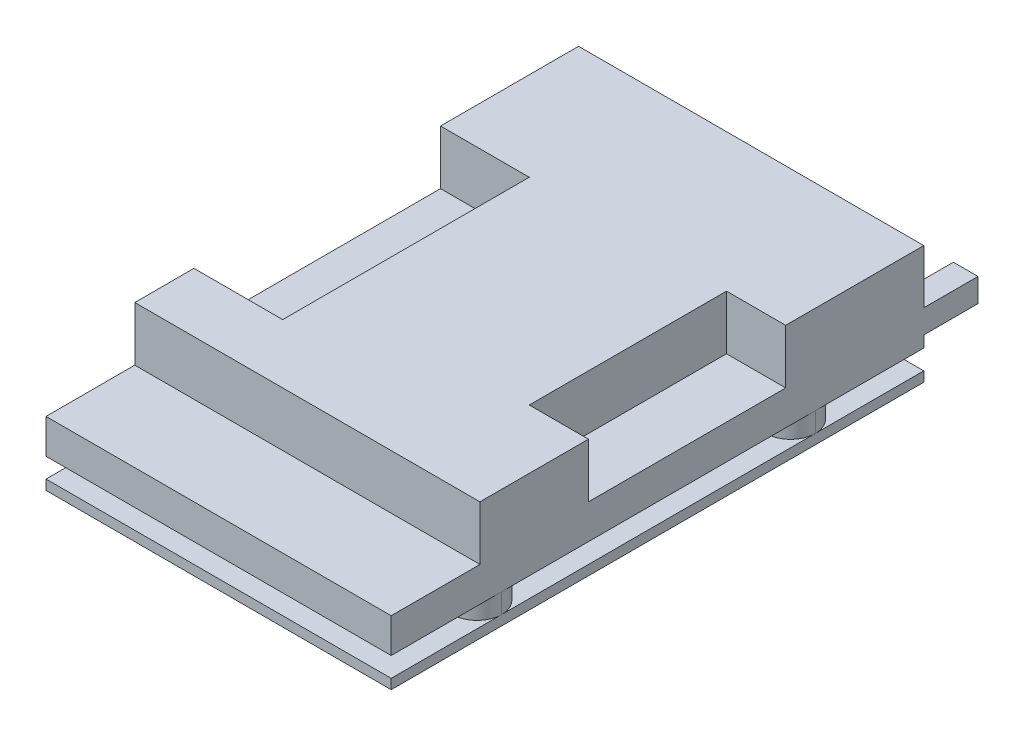
SolidWorks part; units mm, degrees
ref_plane "Front Plane" through (0, 0, 0) normal (0, 0, 1) x (1, 0, 0)
ref_plane "Top Plane" through (0, 0, 0) normal (0, 1, 0) x (1, 0, 0)
ref_plane "Right Plane" through (0, 0, 0) normal (1, 0, 0) x (0, 0, -1)
sketch "Sketch1" plane through (0, 0, 0) normal (0, 1, 0) x (1, 0, 0)
  line L1 (17.5, 27) -> (-17.5, 27)
  line L2 (17.5, 27) -> (17.5, -27)
  line L3 (17.5, -27) -> (-17.5, -27)
  line L4 (-17.5, 27) -> (-17.5, -27)
  line L5 (17.5, 27) -> (-17.5, -27) construction
  line L6 (17.5, -27) -> (-17.5, 27) construction
  point P0 (0, 0)
  dimension "D1" = 54
  dimension "D2" = 35
extrude "Boss-Extrude1" add sketch "Sketch1" along normal blind 12 contours L4 L3 L2 L1
sketch "Sketch2" plane through (0, 12, 0) normal (0, 1, 0) x (1, 0, 0)
  line L0 (17.5, 27) -> (17.5, -27) construction
  line L1 (-17.5, -27) -> (17.5, -27)
  line L2 (-17.5, -27) -> (-17.5, -18)
  line L3 (-17.5, -18) -> (17.5, -18)
  line L4 (17.5, -27) -> (17.5, -18)
  line L5 (-17.5, 27) -> (-17.5, -27) construction
  line L6 (-17.5, -12) -> (-8.5, -12)
  line L7 (-17.5, -12) -> (-17.5, 13)
  line L8 (-17.5, 13) -> (-8.5, 13)
  line L9 (-8.5, -12) -> (-8.5, 13)
  line L11 (17.5, 13) -> (11.5, 13)
  line L12 (17.5, 13) -> (17.5, -7)
  line L13 (17.5, -7) -> (11.5, -7)
  line L14 (11.5, 13) -> (11.5, -7)
  point P17 (17.5, 13.6612)
  dimension "D1" = 9
  dimension "D2" = 9
  dimension "D3" = 6
  dimension "D4" = 25
  dimension "D5" = 20
  dimension "D6" = 6
  dimension "D7" = 11
extrude "Cut-Extrude1" cut sketch "Sketch2" against normal blind 5.5
sketch "Sketch3" plane through (0, 0, -27) normal (0, 0, -1) x (-1, 0, 0)
  line L0 (-17.5, 0) -> (17.5, 0) construction
  line L1 (-12.5, 1) -> (12.5, 1)
  line L2 (-12.5, 1) -> (-12.5, 3)
  line L3 (-12.5, 3) -> (12.5, 3)
  line L4 (12.5, 1) -> (12.5, 3)
  line L5 (-17.5, 12) -> (-17.5, 0) construction
  line L6 (17.5, 12) -> (17.5, 0) construction
  dimension "D1" = 2
  dimension "D2" = 1
  dimension "D3" = 5
  dimension "D4" = 5
extrude "Cut-Extrude2" cut sketch "Sketch3" against normal through all both and the other way through all
sketch "Sketch4" plane through (-17.5, 0, 0) normal (-1, 0, 0) x (0, 0, 1)
  line L0 (27, 1) -> (-27, 1) construction
  line L1 (27, 1) -> (-27, 1)
  line L3 (-27, 1) -> (-18.5, 1)
  line L4 (-27, 1) -> (-27, 3)
  line L5 (-27, 3) -> (-18.5, 3)
  line L6 (-18.5, 1) -> (-18.5, 3)
  line L7 (-13.5, 1) -> (13.3, 1)
  line L8 (-13.5, 1) -> (-13.5, 3)
  line L9 (-13.5, 3) -> (13.3, 3)
  line L10 (13.3, 1) -> (13.3, 3)
  line L11 (27, 1) -> (18.3, 1)
  line L12 (27, 1) -> (27, 3)
  line L13 (27, 3) -> (18.3, 3)
  line L14 (18.3, 1) -> (18.3, 3)
  point P12 (0, 0)
  point P13 (0, 0)
  line M19 (-27, 12) -> (-27, 0)
  line M21 (27, 0) -> (27, 6.5)
  dimension "D1" = 5
  dimension "D2" = 5
  dimension "D3" = 2
  dimension "D4" = 8.5
  dimension "D5" = 8.7
extrude "Cut-Extrude3" cut sketch "Sketch4" against normal through all both and the other way through all contours L1 L6 L5 M19 | L1 L10 L9 L8 | L14 L1 L13 M21 region at (-17.5, 2, -22.75) region at (-17.5, 2, -0.1) region at (-17.5, 2, 22.65)
fillet "Fillet1" radius 2.5 16 edges at (12.5, 2, -13.5) (12.5, 2, -18.5) (17.5, 2, -18.5) (17.5, 2, -13.5) (12.5, 2, 13.3) (12.5, 2, 18.3) (17.5, 2, 13.3) (17.5, 2, 18.3) (-12.5, 2, 13.3) (-12.5, 2, 18.3) (-12.5, 2, -18.5) (-12.5, 2, -13.5) (-17.5, 2, 13.3) (-17.5, 2, 18.3) (-17.5, 2, -18.5) (-17.5, 2, -13.5)
sketch "Sketch5" plane through (0, 0, -27) normal (0, 0, -1) x (-1, 0, 0)
  line L0 (-17.5, 12) -> (-17.5, 3) construction
  line L1 (-17.5, 4.1507) -> (-15, 4.1507)
  line L2 (-17.5, 4.1507) -> (-17.5, 6.54)
  line L3 (-17.5, 6.54) -> (-15, 6.54)
  line L4 (-15, 4.1507) -> (-15, 6.54)
  line L6 (-2.4617, 6.0694) -> (-0.8326, 6.0694)
  line L7 (-2.4617, 6.0694) -> (-2.4617, 4.4041)
  line L8 (-2.4617, 4.4041) -> (-0.8326, 4.4041)
  line L9 (-0.8326, 6.0694) -> (-0.8326, 4.4041)
  line L10 (3.9822, 6.0694) -> (5.394, 6.0694)
  line L11 (3.9822, 6.0694) -> (3.9822, 4.4041)
  line L12 (3.9822, 4.4041) -> (5.394, 4.4041)
  line L13 (5.394, 6.0694) -> (5.394, 4.4041)
  line L14 (14.2272, 6.0694) -> (16.8337, 6.0694)
  line L15 (14.2272, 6.0694) -> (14.2272, 4.1507)
  line L16 (14.2272, 4.1507) -> (16.8337, 4.1507)
  line L17 (16.8337, 6.0694) -> (16.8337, 4.1507)
extrude "Boss-Extrude2" add sketch "Sketch5" along normal blind 5.5
